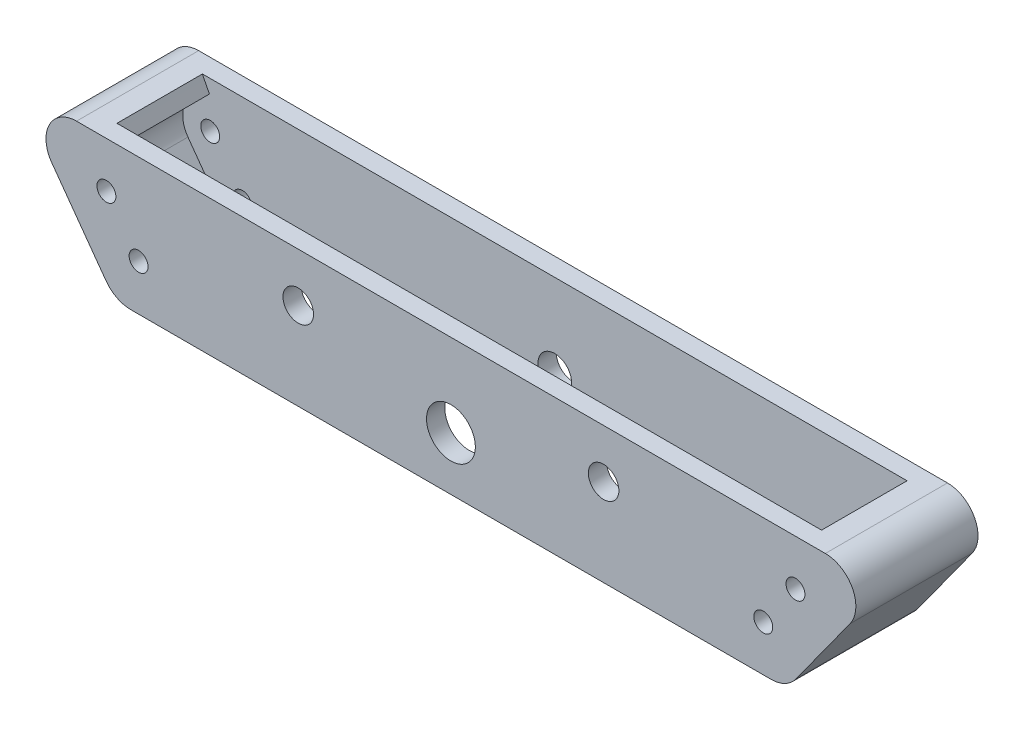
SolidWorks part; units mm, degrees
ref_plane "Front Plane" through (0, 0, 0) normal (0, 0, 1) x (1, 0, 0)
ref_plane "Top Plane" through (0, 0, 0) normal (0, 1, 0) x (1, 0, 0)
ref_plane "Right Plane" through (0, 0, 0) normal (1, 0, 0) x (0, 0, -1)
sketch "Sketch1" plane through (0, 0, 0) normal (0, 0, 1) x (1, 0, 0)
  line L0 (0, 0) -> (0, -62.5) construction
  line L1 (-71.0874, -27.7045) -> (0, -27.7045) construction
  line L2 (0, -50) -> (-54.9811, -50) construction
  line L3 (-54.9811, -50) -> (-71.0874, -27.7045) construction
  line L4 (-56.4171, -35.2045) -> (-51.1468, -42.5) construction
  line L5 (-71.0874, -27.7045) -> (-54.9811, -50)
  line L6 (-54.9811, -50) -> (-39.95, -50)
  line L7 (-71.0874, -27.7045) -> (-57.6928, -27.7045)
  line L8 (54.9811, -50) -> (39.95, -50)
  line L9 (71.0874, -27.7045) -> (54.9811, -50)
  line L10 (71.0874, -27.7045) -> (57.6928, -27.7045)
  line L11 (-58.7994, -31.3868) -> (-56.5441, -29.9795)
  line L12 (48.7646, -46.3177) -> (45.9424, -44.5566)
  line L13 (-56.4171, -35.2045) -> (0, 0) construction
  line L14 (-60.0649, -37.8397) -> (-54.7946, -45.1351)
  line L15 (-48.7646, -46.3177) -> (-45.9424, -44.5566)
  line L16 (60.0649, -37.8397) -> (54.7946, -45.1351)
  line L17 (58.7994, -31.3868) -> (56.5441, -29.9795)
  circle A0 centre (0, 0) radius 62.5 construction
  circle A2 centre (0, -41.25) radius 4
  circle A3 centre (-56.4171, -35.2045) radius 4 construction
  circle A4 centre (-51.1468, -42.5) radius 4 construction
  circle A5 centre (-56.4171, -35.2045) radius 1.55
  circle A6 centre (-51.1468, -42.5) radius 1.55
  circle A7 centre (0, -41.25) radius 15
  circle A8 centre (0, 0) radius 55.5 construction
  circle A9 centre (0, 0) radius 56.25 construction
  circle A10 centre (0, 0) radius 64 construction
  arc A11 (-57.6928, -27.7045) -> (-39.95, -50) centre (0, 0) ccw
  arc A12 (57.6928, -27.7045) -> (39.95, -50) centre (0, 0) cw
  circle A13 centre (51.1468, -42.5) radius 1.55
  circle A14 centre (56.4171, -35.2045) radius 1.55
  circle A15 centre (-56.4171, -35.2045) radius 4.5 construction
  arc A16 (-58.7994, -31.3868) -> (-60.0649, -37.8397) centre (-56.4171, -35.2045) ccw
  circle A17 centre (-51.1468, -42.5) radius 4.5 construction
  arc A18 (-48.7646, -46.3177) -> (-54.7946, -45.1351) centre (-51.1468, -42.5) cw
  arc A19 (48.7646, -46.3177) -> (54.7946, -45.1351) centre (51.1468, -42.5) ccw
  arc A20 (58.7994, -31.3868) -> (60.0649, -37.8397) centre (56.4171, -35.2045) cw
  dimension "D1" = 125
  dimension "D3" = 8
  dimension "D4" = 8
  dimension "D9" = 3.1
  dimension "D11" = 30
  dimension "D12" = 112.5
  dimension "D13" = 128
  dimension "D14" = 9
  dimension "D15" = 9
  dimension "D5" = 9
  dimension "D6" = 20
  dimension "D7" = 7.5
  dimension "D8" = 7.5
  dimension "D10" = 7.5
  dimension "D2" = 7
extrude "Boss-Extrude1" add sketch "Sketch1" along normal mid plane 14 contours A11 L7 L5 L6 A6 A5 | L10 A12 L8 L9 A13 A14 region at (-64.3901, -28.0875, 0) region at (47.4655, -49.617, 0)
sketch "Sketch2" plane through (0, 0, 7) normal (0, 0, 1) x (1, 0, 0)
  line L0 (-54.9811, -50) -> (54.9811, -50)
  line L1 (54.9811, -50) -> (71.0874, -27.7045)
  line L2 (71.0874, -27.7045) -> (-71.0874, -27.7045)
  line L3 (-71.0874, -27.7045) -> (-54.9811, -50)
  circle A0 centre (0, -41.25) radius 4 construction
  circle A1 centre (0, -41.25) radius 4
  circle A10 centre (-51.1468, -42.5) radius 1.55 construction
  circle A11 centre (-56.4171, -35.2045) radius 1.55 construction
  circle A12 centre (-51.1468, -42.5) radius 1.55
  circle A13 centre (-56.4171, -35.2045) radius 1.55
  circle A14 centre (56.4171, -35.2045) radius 1.55 construction
  circle A15 centre (51.1468, -42.5) radius 1.55 construction
  circle A16 centre (56.4171, -35.2045) radius 1.55
  circle A17 centre (51.1468, -42.5) radius 1.55
extrude "Boss-Extrude2" add sketch "Sketch2" along normal blind 3
mirror "Mirror2" about plane through (0, 0, 0) normal (0, 0, 1) of "Boss-Extrude2"
fillet "Fillet1" radius 5 4 edges at (-54.9811, -50, 0) (54.9811, -50, 0) (71.0874, -27.7045, 0) (-71.0874, -27.7045, 0)
fillet "Fillet2" radius 1 2 edges at (39.95, -50, 0) (-39.95, -50, 0)
sketch "Sketch3" plane through (0, 0, -10) normal (0, 0, -1) x (-1, 0, 0)
  circle A0 centre (0, -41.25) radius 2.75
  circle A1 centre (0, -41.25) radius 6.0148
  dimension "D1" = 5.5
extrude "Boss-Extrude3" add sketch "Sketch3" against normal up to surface (3 mm away) up to face at (0, -40.2617, -7)
sketch "Sketch4" plane through (0, 0, 10) normal (0, 0, 1) x (1, 0, 0)
  line L0 (0, -27.7045) -> (0, -50) construction
  line L1 (-71.0874, -27.7045) -> (0, -27.7045) construction
  circle A0 centre (-25, -35.7045) radius 2.5
  circle A1 centre (25, -35.7045) radius 2.5
  dimension "D1" = 5
  dimension "D2" = 8
  dimension "D3" = 25
extrude "Cut-Extrude1" cut sketch "Sketch4" against normal blind 10
equation "\"D12@Sketch1\"=75*1.5"
equation "\"D11@Sketch1\"=20*1.5"
